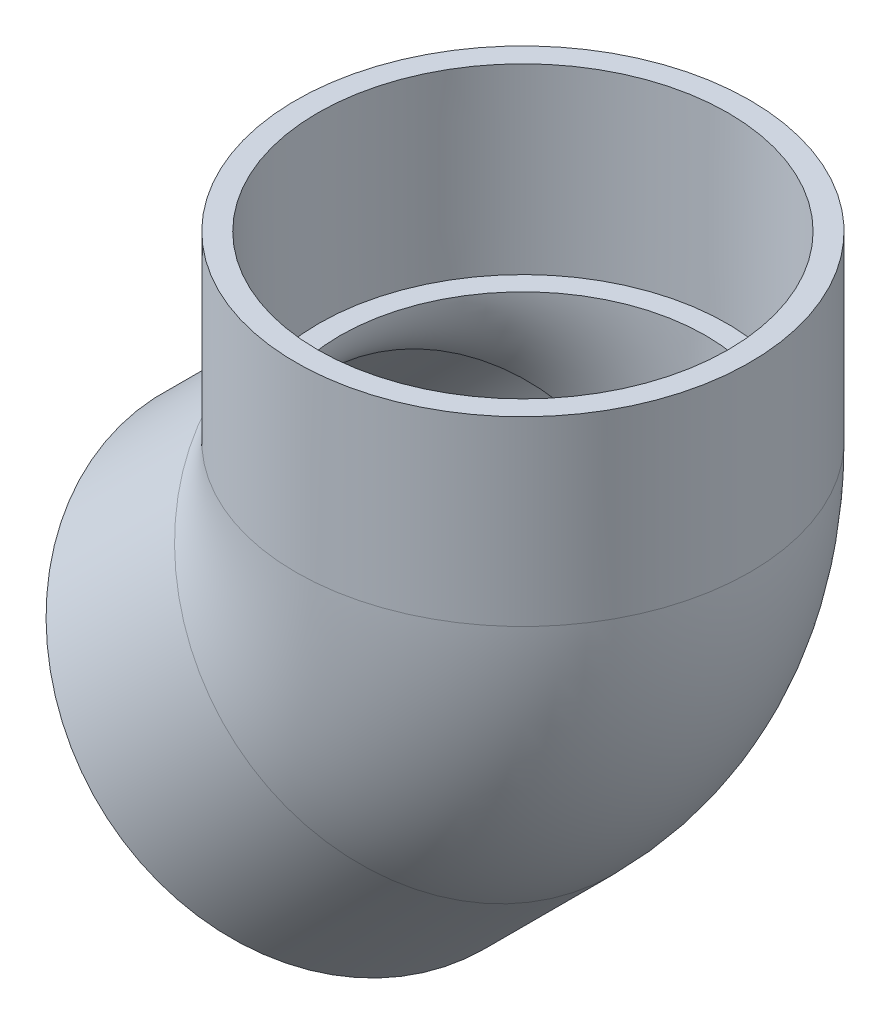
SolidWorks part; units mm, degrees
ref_plane "Front Plane" through (0, 0, 0) normal (0, 0, 1) x (1, 0, 0)
ref_plane "Top Plane" through (0, 0, 0) normal (0, 1, 0) x (1, 0, 0)
ref_plane "Right Plane" through (0, 0, 0) normal (1, 0, 0) x (0, 0, -1)
sketch "ElbowArc" plane through (0, 0, 0) normal (0, 0, 1) x (1, 0, 0)
  line L0 (-55.5653, -55.5653) -> (0, 0) construction
  line L1 (0, 0) -> (0, 78.5812) construction
  line L2 (-19.6443, -19.6443) -> (0, 0) construction
  line L3 (0, 0) -> (0, 27.7812) construction
  line L4 (-100.4666, -10.6641) -> (-10.6641, -100.4666) construction
  line L5 (-59.9746, 20.686) -> (-96.1381, -14.9925) construction
  line L6 (-59.9746, 20.686) -> (20.686, -59.9746) construction
  line L7 (20.686, -59.9746) -> (-14.9925, -96.1381) construction
  line L8 (-96.1381, -14.9925) -> (-14.9925, -96.1381) construction
  line L9 (-63.5, 78.5812) -> (63.5, 78.5812) construction
  line L10 (-57.3786, 78.5812) -> (57.3786, 78.5812) construction
  line L11 (57.3786, 78.5812) -> (57.0357, 27.7812) construction
  line L12 (57.0357, 27.7812) -> (-57.0357, 27.7812) construction
  line L13 (-57.0357, 27.7812) -> (-57.3786, 78.5812) construction
  line L14 (-55.7988, 16.5102) -> (16.5102, -55.7988) construction
  line L18 (-51.1302, 27.7812) -> (51.1302, 27.7812) construction
  arc A0 (0, 27.7812) -> (-19.6443, -19.6443) centre (-67.0699, 27.7812) cw construction
  dimension "BendRadius" = 78.5812
  dimension "J" = 27.7812
  dimension "M" = 127
  dimension "OD A" = 114.7572
  dimension "OD B" = 114.0714
  dimension "ID" = 102.2604
  dimension "BendAngle" = 45
sketch "Sketch1" plane through (0, 0, 0) normal (0, 0, 1) x (1, 0, 0)
  line L0 (-55.5653, -55.5653) -> (0, 0) construction
  line L1 (-55.5653, -55.5653) -> (0, 0) construction
  line L3 (-10.6641, -100.4666) -> (25.257, -64.5456)
  line L4 (-10.6641, -100.4666) -> (-14.9925, -96.1381)
  line L5 (-14.9925, -96.1381) -> (20.686, -59.9746)
  line L6 (25.257, -64.5456) -> (20.686, -59.9746)
revolve "Revolve1" add sketch "Sketch1" angle 360 about L1
sketch "Sketch2" plane through (0, 0, 0) normal (0, 0, 1) x (1, 0, 0)
  line L0 (57.3786, 78.5812) -> (57.0357, 27.7812)
  line L1 (57.0357, 27.7812) -> (63.5, 27.7812)
  line L2 (63.5, 27.7812) -> (63.5, 78.5812)
  line L3 (63.5, 78.5812) -> (57.3786, 78.5812)
  line L4 (0, 0) -> (0, 78.5812) construction
  line L5 (0, 0) -> (0, 78.5812) construction
revolve "Revolve2" add sketch "Sketch2" angle 360 about L5
sketch "Sketch3" plane through (-19.6443, -19.6443, 0) normal (0.7071, 0.7071, 0) x (0, 0, -1)
  circle A0 centre (0, 0) radius 51.1302
  circle A1 centre (0, 0) radius 63.5
sketch "Sketch4" plane through (0, 0, 0) normal (0, 0, 1) x (1, 0, 0)
  line L0 (-55.5653, -55.5653) -> (0, 0) construction
  line L1 (0, 0) -> (0, 78.5812) construction
  line L2 (-55.5653, -55.5653) -> (-19.6443, -19.6443) construction
  line L3 (0, 27.7813) -> (0, 78.5812) construction
  arc A0 (-19.6443, -19.6443) -> (0, 27.7813) centre (-67.0699, 27.7813) ccw
sweep "Sweep1" add profiles "Sketch3" path "Sketch4"
other "CPoint1" parameters "Diameter"=101.6, "StubLength"=76.2
ref_axis "Axis1" through (0, 37.7813, 0) along (0, -1, 0)
other "CPoint2" parameters "Diameter"=101.6, "StubLength"=152.4
ref_axis "Axis2" through (-26.7154, -26.7154, 0) along (0.7071, 0.7071, 0)
other "RPoint1"
